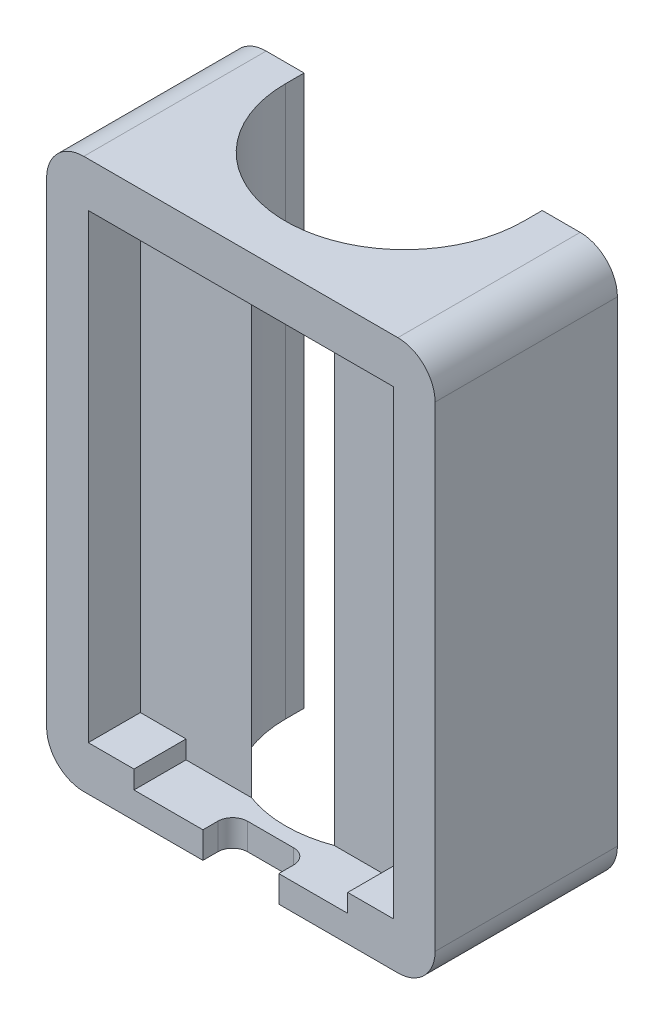
SolidWorks part; units mm, degrees
ref_plane "Plan de face" through (0, 0, 0) normal (0, 0, 1) x (1, 0, 0)
ref_plane "Plan de dessus" through (0, 0, 0) normal (0, 1, 0) x (1, 0, 0)
ref_plane "Plan de droite" through (0, 0, 0) normal (1, 0, 0) x (0, 0, -1)
sketch "Esquisse1" plane through (0, 0, 0) normal (0, 0, 1) x (1, 0, 0)
  line L1 (-41.2248, -2.0065) -> (10.9752, -2.0065)
  line L2 (-41.2248, -2.0065) -> (-41.2248, -82.0065)
  line L3 (-41.2248, -82.0065) -> (10.9752, -82.0065)
  line L4 (10.9752, -2.0065) -> (10.9752, -82.0065)
extrude "Boss.-Extru.2" add sketch "Esquisse1" along normal blind 22
sketch "Esquisse2" plane through (0, -82.0065, 0) normal (0, -1, 0) x (1, 0, 0)
  line L0 (-41.2248, 0) -> (10.9752, 0) construction
  circle A0 centre (-15.1248, 0) radius 16
sketch "Esquisse3" plane through (0, 0, 22) normal (0, 0, 1) x (1, 0, 0)
  line L0 (-41.2248, -2.0065) -> (-41.2248, -82.0065) construction
  line L1 (-39.4848, -5.5677) -> (9.2352, -5.5677)
  line L2 (-39.4848, -5.5677) -> (-39.4848, -78.4453)
  line L3 (-39.4848, -78.4453) -> (9.2352, -78.4453)
  line L4 (9.2352, -5.5677) -> (9.2352, -78.4453)
  line L5 (10.9752, -82.0065) -> (10.9752, -2.0065) construction
  line L6 (10.9752, -2.0065) -> (-41.2248, -2.0065) construction
  line L7 (-31.1248, -82.0065) -> (0.8752, -82.0065) construction
  dimension "D1" = 1.74
  dimension "D2" = 1.74
  dimension "D3" = 3.5612
  dimension "D4" = 3.5612
extrude "Enlèv. mat.-Extru.1" cut sketch "Esquisse3" against normal blind 5
fillet "Congé1" radius 10 4 edges at (-39.4848, -78.4453, 19.5) (9.2352, -78.4453, 19.5) (9.2352, -5.5677, 19.5) (-39.4848, -5.5677, 19.5)
sketch "Esquisse5" plane through (0, 0, 17) normal (0, 0, 1) x (1, 0, 0)
  line L0 (-35.6248, -42.0065) -> (5.3752, -42.0065) construction
  line L1 (-35.6248, -8.0065) -> (5.3752, -8.0065)
  line L2 (-35.6248, -8.0065) -> (-35.6248, -15.5677)
  line L3 (-35.6248, -76.0065) -> (-29.4848, -76.0065)
  line L4 (5.3752, -8.0065) -> (5.3752, -15.5677)
  line L5 (10.9752, -2.0065) -> (-41.2248, -2.0065) construction
  line L6 (5.3752, -68.4453) -> (5.3752, -76.0065)
  line L7 (-0.7648, -76.0065) -> (5.3752, -76.0065)
  line L8 (-29.4848, -8.0065) -> (-0.7648, -8.0065)
  line L9 (10.9752, -82.0065) -> (10.9752, -2.0065) construction
  line L10 (-35.6248, -68.4453) -> (-35.6248, -15.5677)
  line L11 (5.3752, -15.5677) -> (5.3752, -68.4453)
  line L13 (-35.6248, -15.5677) -> (-35.6248, -8.0065)
  line L15 (-29.4848, -8.0065) -> (-35.6248, -8.0065)
  line L16 (-39.4848, -15.5677) -> (-39.4848, -5.5677)
  line L17 (-39.4848, -5.5677) -> (-29.4848, -5.5677)
  line L18 (-15.1248, -8.0065) -> (-15.1248, -76.0065) construction
  line L26 (9.2352, -15.5677) -> (9.2352, -5.5677)
  line L27 (9.2352, -5.5677) -> (-0.7648, -5.5677)
  line L29 (9.2352, -68.4453) -> (9.2352, -78.4453)
  line L30 (9.2352, -78.4453) -> (-0.7648, -78.4453)
  line L31 (-0.7648, -78.4453) -> (-0.7648, -76.0065)
  line L33 (-29.4848, -78.4453) -> (-29.4848, -76.0065)
  line L34 (-39.4848, -78.4453) -> (-29.4848, -78.4453)
  line L35 (-39.4848, -68.4453) -> (-39.4848, -78.4453)
  line L36 (-35.6248, -68.4453) -> (-35.6248, -76.0065)
  line M5 (-39.4848, -15.5677) -> (-39.4848, -68.4453)
  arc M6 (-39.4848, -68.4453) -> (-29.4848, -78.4453) centre (-29.4848, -68.4453) ccw
  arc M8 (-0.7648, -78.4453) -> (9.2352, -68.4453) centre (-0.7648, -68.4453) ccw
  line M9 (9.2352, -68.4453) -> (9.2352, -15.5677)
  arc M10 (9.2352, -15.5677) -> (-0.7648, -5.5677) centre (-0.7648, -15.5677) ccw
  line M11 (-0.7648, -5.5677) -> (-29.4848, -5.5677)
  arc M12 (-29.4848, -5.5677) -> (-39.4848, -15.5677) centre (-29.4848, -15.5677) ccw
  dimension "D1" = 41
  dimension "D2" = 68
  dimension "D3" = 6
  dimension "D4" = 5.6
extrude "Boss.-Extru.4" add sketch "Esquisse5" along normal blind 5 contours L36 L10 L2 L1 L4 L11 L6 L7 L31 L33 L3 M8 M9 M10 M11 M12 M5 M6 region at (-36.5014, -11.7871, 17)
extrude "Enlèv. mat.-Extru.3" cut sketch "Esquisse2" against normal through all contours A0
sketch "Esquisse7" plane through (0, 0, 17) normal (0, 0, 1) x (1, 0, 0)
  line L0 (-35.6248, -8.0065) -> (5.3752, -8.0065)
  line L1 (5.3752, -8.0065) -> (5.3752, -76.0065)
  line L2 (5.3752, -76.0065) -> (-0.7648, -76.0065)
  line L3 (-0.7648, -76.0065) -> (-0.7648, -78.4453)
  line L4 (-0.7648, -78.4453) -> (-29.4848, -78.4453)
  line L5 (-29.4848, -78.4453) -> (-29.4848, -76.0065)
  line L6 (-29.4848, -76.0065) -> (-35.6248, -76.0065)
  line L7 (-35.6248, -76.0065) -> (-35.6248, -8.0065)
extrude "Enlèv. mat.-Extru.5" cut sketch "Esquisse7" against normal blind 2
sketch "Esquisse8" plane through (0, 0, 22) normal (0, 0, 1) x (1, 0, 0)
  line L1 (-20.2198, -78.4453) -> (-10.0298, -78.4453)
  line L2 (-20.2198, -78.4453) -> (-20.2198, -82.0065)
  line L3 (-20.2198, -82.0065) -> (-10.0298, -82.0065)
  line L4 (-10.0298, -78.4453) -> (-10.0298, -82.0065)
  line L5 (-29.4848, -78.4453) -> (-29.4848, -76.0065) construction
  line L7 (-0.7648, -78.4453) -> (-0.7648, -76.0065) construction
  dimension "D1" = 9.265
  dimension "D2" = 9.265
sketch "Esquisse11" plane through (0, -8.0065, 0) normal (0, -1, 0) x (1, 0, 0)
  line L0 (-20.6926, 15) -> (-35.6248, 15)
  line L1 (5.3752, 22) -> (-35.6248, 22)
  line L2 (5.3752, 22) -> (5.3752, 15)
  line L3 (5.3752, 15) -> (-9.557, 15)
  line L4 (-35.6248, 22) -> (-35.6248, 15)
  arc A0 (-9.557, 15) -> (-20.6926, 15) centre (-15.1248, 0) ccw
extrude "Boss.-Extru.6" add sketch "Esquisse11" along normal blind 6.07
sketch "Esquisse12" plane through (0, -2.0065, 0) normal (0, 1, 0) x (1, 0, 0)
  line L1 (-41.2248, 0) -> (10.9752, 0)
  line L2 (-41.2248, 0) -> (-41.2248, -22)
  line L3 (-41.2248, -22) -> (10.9752, -22)
  line L4 (10.9752, 0) -> (10.9752, -22)
extrude "Enlèv. mat.-Extru.7" cut sketch "Esquisse12" against normal blind 6.07
extrude "Enlèv. mat.-Extru.6" cut sketch "Esquisse8" against normal blind 4
fillet "Congé3" radius 2 2 edges at (-10.0298, -80.2259, 18) (-20.2198, -80.2259, 18)
sketch "Esquisse9" plane through (0, 0, 0) normal (0, 0, -1) x (-1, 0, 0)
  line L0 (31.1248, -8.0765) -> (41.2248, -8.0765) construction
  line L1 (31.1248, -8.0765) -> (41.2248, -8.0765)
  line L2 (31.1248, -8.0765) -> (31.1248, -82.0065)
  line L3 (31.1248, -82.0065) -> (41.2248, -82.0065)
  line L4 (41.2248, -8.0765) -> (41.2248, -82.0065)
  line L5 (-10.9752, -8.0765) -> (-0.8752, -8.0765)
  line L6 (-10.9752, -8.0765) -> (-10.9752, -82.0065)
  line L7 (-10.9752, -82.0065) -> (-0.8752, -82.0065)
  line L8 (-0.8752, -8.0765) -> (-0.8752, -82.0065)
  line L10 (-10.9752, -8.0765) -> (-0.8752, -8.0765) construction
extrude "Boss.-Extru.5" add sketch "Esquisse9" along normal blind 2.5
fillet "Congé4" radius 5 4 edges at (10.9752, -82.0065, 9.75) (-41.2248, -82.0065, 9.75) (-41.2248, -8.0765, 9.75) (10.9752, -8.0765, 9.75)
